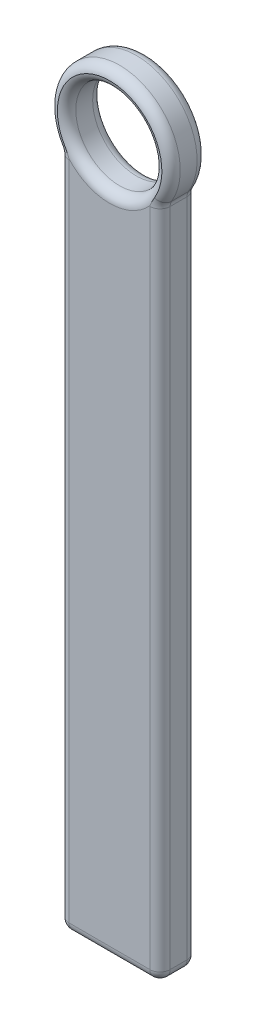
SolidWorks part; units mm, degrees
ref_plane "Front Plane" through (0, 0, 0) normal (0, 0, 1) x (1, 0, 0)
ref_plane "Top Plane" through (0, 0, 0) normal (0, 1, 0) x (1, 0, 0)
ref_plane "Right Plane" through (0, 0, 0) normal (1, 0, 0) x (0, 0, -1)
sketch "Sketch1" plane through (0, 0, 0) normal (0, 0, 1) x (1, 0, 0)
  line L0 (-15, -9.9499) -> (-15, -209.9499)
  line L1 (-15, -209.9499) -> (15, -209.9499)
  line L2 (15, -209.9499) -> (15, -9.9499)
  line L3 (0, 25.4552) -> (0, -122.2022) construction
  circle A0 centre (0, 0) radius 13
  arc A2 (-15, -9.9499) -> (15, -9.9499) centre (0, 0) cw
  dimension "D1" = 26
  dimension "D2" = 18
  dimension "D3" = 200
  dimension "D4" = 30
extrude "Boss-Extrude1" add sketch "Sketch1" along normal mid plane 11
fillet "Fillet2" radius 3 14 edges at (0, 18, -5.5) (13, 0, -5.5) (15, -9.9499, 0) (15, -109.9499, -5.5) (13, 0, 5.5) (15, -109.9499, 5.5) (0, 18, 5.5) (0, -209.9499, 5.5) (15, -209.9499, 0) (0, -209.9499, -5.5) (-15, -9.9499, 0) (-15, -109.9499, 5.5) (-15, -209.9499, 0) (-15, -109.9499, -5.5)
